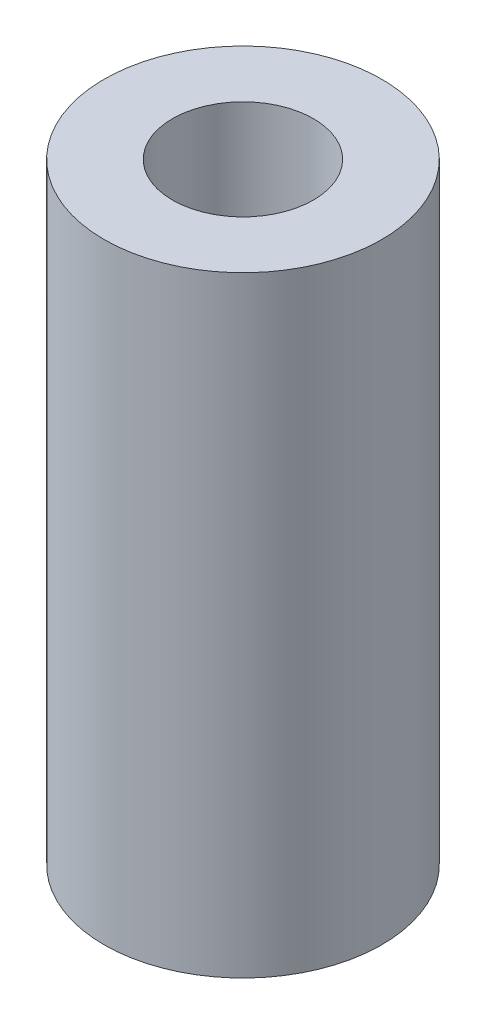
SolidWorks part; units mm, degrees
ref_plane "Front Plane" through (0, 0, 0) normal (0, 0, 1) x (1, 0, 0)
ref_plane "Top Plane" through (0, 0, 0) normal (0, 1, 0) x (1, 0, 0)
ref_plane "Right Plane" through (0, 0, 0) normal (1, 0, 0) x (0, 0, -1)
sketch "Sketch1" plane through (0, 0, 0) normal (0, 1, 0) x (1, 0, 0)
  circle A0 centre (0, 0) radius 6.35
  arc A4 (5.5726, 3.0445) -> (-6.3197, -0.62) centre (0, 0) ccw construction
  circle A5 centre (0, 0) radius 3.2258
  circle A6 centre (0, 0) radius 3.2258
  dimension "D1" = 0.0508
extrude "Boss-Extrude1" add sketch "Sketch1" along normal up to surface (27.9373 mm away)
